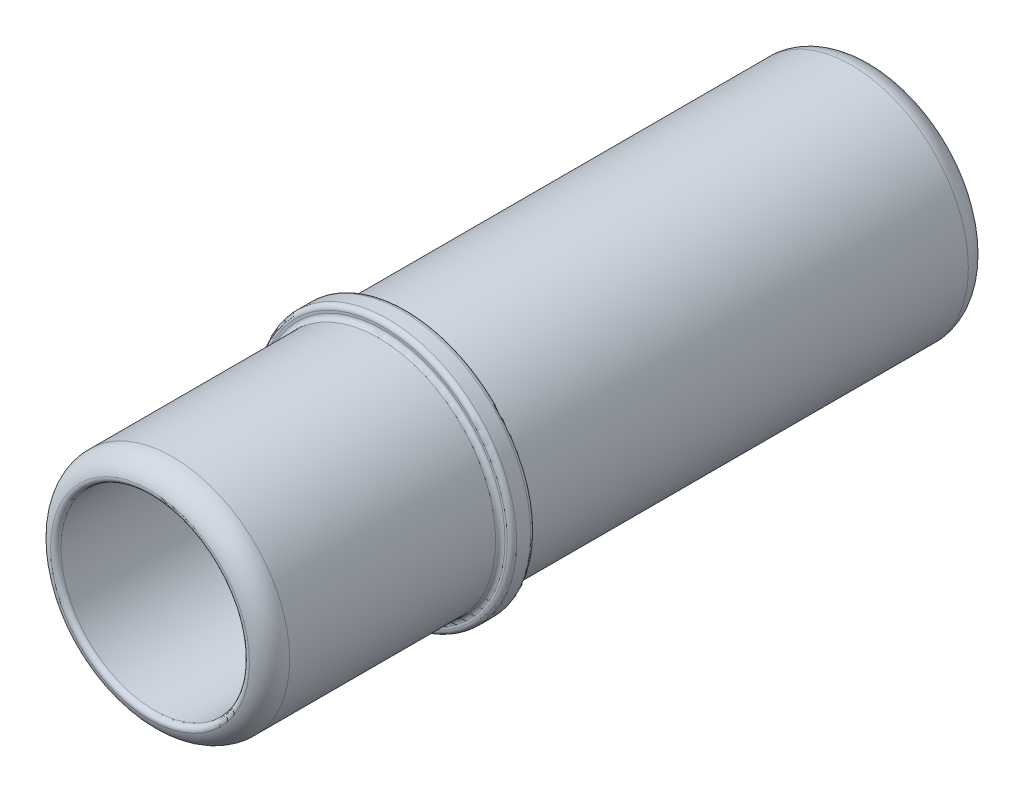
SolidWorks part; units mm, degrees
ref_plane "Front Plane" through (0, 0, 0) normal (0, 0, 1) x (1, 0, 0)
ref_plane "Top Plane" through (0, 0, 0) normal (0, 1, 0) x (1, 0, 0)
ref_plane "Right Plane" through (0, 0, 0) normal (1, 0, 0) x (0, 0, -1)
sketch "Sketch1" plane through (0, 0, 0) normal (0, 0, 1) x (1, 0, 0)
  circle A0 centre (0, 0) radius 0.55
  dimension "D1" = 1.1
extrude "Boss-Extrude1" add sketch "Sketch1" along normal blind 0.1
sketch "Sketch2" plane through (0, 0, 0.1) normal (0, 0, 1) x (1, 0, 0)
  circle A0 centre (0, 0) radius 0.5
extrude "Boss-Extrude2" add sketch "Sketch2" along normal blind 1 contours A0
sketch "Sketch3" plane through (0, 0, 0) normal (0, 0, -1) x (-1, 0, 0)
  circle A0 centre (0, 0) radius 0.5
extrude "Boss-Extrude3" add sketch "Sketch3" along normal blind 2
sketch "Sketch4" plane through (0, 0, -2) normal (0, 0, -1) x (-1, 0, 0)
  circle A0 centre (0, 0) radius 0.4
extrude "Cut-Extrude1" cut sketch "Sketch4" against normal blind 3.1
fillet "Fillet1" radius 0.1 1 edges at (-0.5, 0, -2) type face fillet first side face at (-0.4, 0, -2) second side face at (-0.5, 0, -2)
fillet "Fillet2" radius 0.1 1 edges at (0.5, 0, 1.1) type face fillet first side face at (-0.4, 0, 1.1) second side face at (0.5, 0, 1.1)
fillet "Fillet3" radius 0.02 1 edges at (0.55, 0, 0.1) type face fillet first side face at (0.5, 0, 0.1) second side face at (0.55, 0, 0.1)
fillet "Fillet4" radius 0.02 1 edges at (0.55, 0, 0) type face fillet first side face at (0.5, 0, 0) second side face at (0.55, 0, 0.08)
fillet "Fillet5" radius 0.02 1 edges at (0.5, 0, 0) type face fillet first side face at (-0.5, 0, -1.9) second side face at (0.53, 0, 0)
fillet "Fillet6" radius 0.02 1 edges at (0.5, 0, 0.1) type face fillet first side face at (0.5, 0, 1) second side face at (0.53, 0, 0.1)
fillet "Fillet7" radius 0.02 1 edges at (-0.4, 0, -2) type face fillet first side face at (-0.4, 0, 1.1) second side face at (-0.4, 0, -2)
fillet "Fillet8" radius 0.02 1 edges at (-0.4, 0, 1.1) type face fillet first side face at (0.4, 0, -1.9775) second side face at (-0.4, 0, 1.1)
